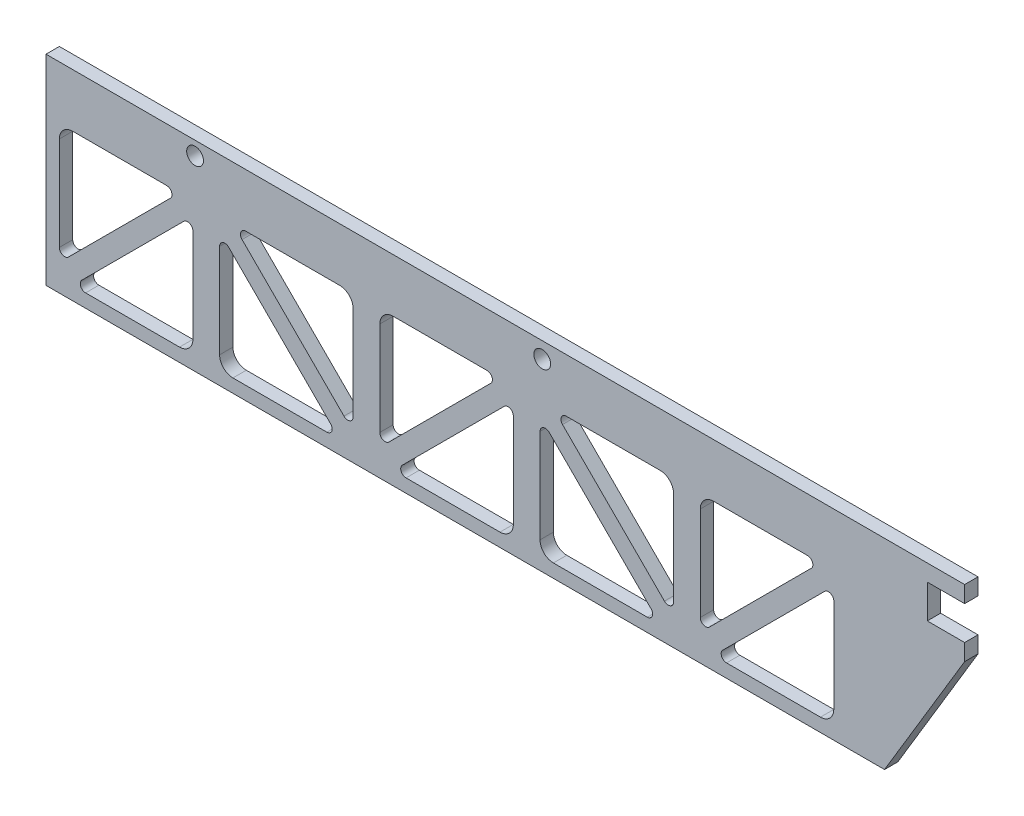
SolidWorks part; units mm, degrees
material "Balsa"
ref_plane "Front Plane" through (0, 0, 0) normal (0, 0, 1) x (1, 0, 0)
ref_plane "Top Plane" through (0, 0, 0) normal (0, 1, 0) x (1, 0, 0)
ref_plane "Right Plane" through (0, 0, 0) normal (1, 0, 0) x (0, 0, -1)
sketch "Model" plane through (0, 0, 0) normal (0, 0, 1) x (1, 0, 0)
  line L8 (171.2321, 6.35) -> (215.9, 6.35)
  line L9 (217.9139, 59.1639) -> (169.4361, 10.6861)
  line L10 (222.25, 57.3679) -> (222.25, 12.7)
  line L11 (234.95, 57.3679) -> (234.95, 12.7)
  line L12 (239.2861, 59.1639) -> (287.7639, 10.6861)
  line L13 (241.3, 6.35) -> (285.9679, 6.35)
  line L14 (294.1139, 17.0361) -> (245.6361, 65.5139)
  line L15 (247.4321, 69.85) -> (292.1, 69.85)
  line L16 (298.45, 63.5) -> (298.45, 18.8321)
  line L17 (323.6321, 6.35) -> (368.3, 6.35)
  line L18 (370.3139, 59.1639) -> (321.8361, 10.6861)
  line L19 (374.65, 57.3679) -> (374.65, 12.7)
  line L20 (18.8321, 6.35) -> (63.5, 6.35)
  line L21 (17.0361, 10.6861) -> (65.5139, 59.1639)
  line L22 (69.85, 57.3679) -> (69.85, 12.7)
  line L23 (82.55, 57.3679) -> (82.55, 12.7)
  line L24 (86.8861, 59.1639) -> (135.3639, 10.6861)
  line L25 (88.9, 6.35) -> (133.5679, 6.35)
  line L26 (93.2361, 65.5139) -> (141.7139, 17.0361)
  line L27 (95.0321, 69.85) -> (139.7, 69.85)
  line L28 (146.05, 63.5) -> (146.05, 18.8321)
  line L29 (163.0861, 17.0361) -> (211.5639, 65.5139)
  line L30 (158.75, 63.5) -> (158.75, 18.8321)
  line L31 (165.1, 69.85) -> (209.7679, 69.85)
  line L32 (315.4861, 17.0361) -> (363.9639, 65.5139)
  line L33 (311.15, 63.5) -> (311.15, 18.8321)
  line L34 (317.5, 69.85) -> (362.1679, 69.85)
  line L35 (419.1, 87.376) -> (419.1, 71.374)
  line L36 (436.88, 87.376) -> (419.1, 87.376)
  line L37 (436.88, 87.376) -> (436.88, 95.25)
  line L38 (0, 95.25) -> (436.88, 95.25)
  line L39 (0, 0) -> (0, 95.25)
  line L40 (0, 0) -> (398.78, 0)
  line L41 (436.88, 63.5) -> (398.78, 0)
  line L42 (436.88, 63.5) -> (436.88, 71.374)
  line L43 (419.1, 71.374) -> (436.88, 71.374)
  line L44 (6.35, 63.5) -> (6.35, 18.8321)
  line L45 (12.7, 69.85) -> (57.3679, 69.85)
  line L46 (59.1639, 65.5139) -> (10.6861, 17.0361)
  arc A0 (215.9, 6.35) -> (222.25, 12.7) centre (215.9, 12.7) ccw
  arc A1 (169.4361, 10.6861) -> (171.2321, 6.35) centre (171.2321, 8.89) ccw
  arc A2 (222.25, 57.3679) -> (217.9139, 59.1639) centre (219.71, 57.3679) ccw
  arc A3 (239.2861, 59.1639) -> (234.95, 57.3679) centre (237.49, 57.3679) ccw
  arc A4 (285.9679, 6.35) -> (287.7639, 10.6861) centre (285.9679, 8.89) ccw
  arc A5 (234.95, 12.7) -> (241.3, 6.35) centre (241.3, 12.7) ccw
  arc A6 (247.4321, 69.85) -> (245.6361, 65.5139) centre (247.4321, 67.31) ccw
  arc A7 (298.45, 63.5) -> (292.1, 69.85) centre (292.1, 63.5) ccw
  arc A8 (294.1139, 17.0361) -> (298.45, 18.8321) centre (295.91, 18.8321) ccw
  arc A9 (321.8361, 10.6861) -> (323.6321, 6.35) centre (323.6321, 8.89) ccw
  arc A10 (374.65, 57.3679) -> (370.3139, 59.1639) centre (372.11, 57.3679) ccw
  arc A11 (368.3, 6.35) -> (374.65, 12.7) centre (368.3, 12.7) ccw
  arc A12 (63.5, 6.35) -> (69.85, 12.7) centre (63.5, 12.7) ccw
  arc A13 (17.0361, 10.6861) -> (18.8321, 6.35) centre (18.8321, 8.89) ccw
  arc A14 (69.85, 57.3679) -> (65.5139, 59.1639) centre (67.31, 57.3679) ccw
  arc A15 (86.8861, 59.1639) -> (82.55, 57.3679) centre (85.09, 57.3679) ccw
  arc A16 (133.5679, 6.35) -> (135.3639, 10.6861) centre (133.5679, 8.89) ccw
  arc A17 (82.55, 12.7) -> (88.9, 6.35) centre (88.9, 12.7) ccw
  arc A18 (95.0321, 69.85) -> (93.2361, 65.5139) centre (95.0321, 67.31) ccw
  arc A19 (146.05, 63.5) -> (139.7, 69.85) centre (139.7, 63.5) ccw
  arc A20 (141.7139, 17.0361) -> (146.05, 18.8321) centre (143.51, 18.8321) ccw
  arc A21 (158.75, 18.8321) -> (163.0861, 17.0361) centre (161.29, 18.8321) ccw
  arc A22 (165.1, 69.85) -> (158.75, 63.5) centre (165.1, 63.5) ccw
  arc A23 (211.5639, 65.5139) -> (209.7679, 69.85) centre (209.7679, 67.31) ccw
  arc A24 (363.9639, 65.5139) -> (362.1679, 69.85) centre (362.1679, 67.31) ccw
  arc A25 (311.15, 18.8321) -> (315.4861, 17.0361) centre (313.69, 18.8321) ccw
  arc A26 (317.5, 69.85) -> (311.15, 63.5) centre (317.5, 63.5) ccw
  arc A27 (6.35, 18.8321) -> (10.6861, 17.0361) centre (8.89, 18.8321) ccw
  arc A28 (12.7, 69.85) -> (6.35, 63.5) centre (12.7, 63.5) ccw
  arc A29 (59.1639, 65.5139) -> (57.3679, 69.85) centre (57.3679, 67.31) ccw
  circle A30 centre (70.8917, 88.8013) radius 4
  circle A31 centre (235.9917, 87.63) radius 4
  point P92 (0, 0)
  point P93 (0, 0)
  point P109 (243.0748, 95.25)
  point P110 (0, 0)
  dimension "D2" = 6.4487
  dimension "D3" = 70.8917
  dimension "D4" = 8
  dimension "D5" = 7.62
  dimension "D6" = 8
  dimension "D1" = 95.25
  dimension "D7" = 165.1
extrude "Boss-Extrude2" add sketch "Model" along normal blind 6.35
